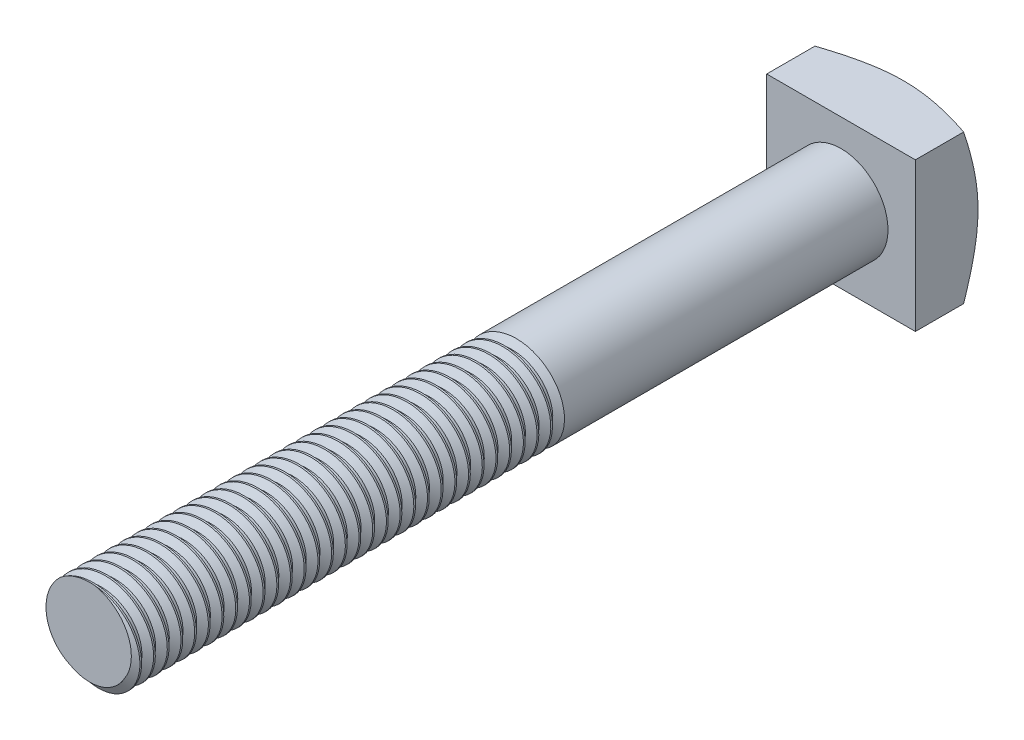
SolidWorks part; units mm, degrees
ref_plane "Front Plane" through (0, 0, 0) normal (0, 0, 1) x (1, 0, 0)
ref_plane "Top Plane" through (0, 0, 0) normal (0, 1, 0) x (1, 0, 0)
ref_plane "Right Plane" through (0, 0, 0) normal (1, 0, 0) x (0, 0, -1)
sketch "Sketch1" plane through (0, 0, 0) normal (0, 0, 1) x (1, 0, 0)
  line L1 (-9.5, -9.5) -> (9.5, -9.5)
  line L2 (-9.5, -9.5) -> (-9.5, 9.5)
  line L3 (-9.5, 9.5) -> (9.5, 9.5)
  line L4 (9.5, -9.5) -> (9.5, 9.5)
  line L5 (-9.5, -9.5) -> (9.5, 9.5) construction
  line L6 (-9.5, 9.5) -> (9.5, -9.5) construction
  point P0 (0, 0)
  dimension "D1" = 19
extrude "Boss-Extrude1" add sketch "Sketch1" along normal blind 8
sketch "Sketch2" plane through (0, 0, 0) normal (0, 1, 0) x (1, 0, 0)
  line L0 (9.5, 0) -> (16.2147, 0)
  line L1 (16.2147, 0) -> (16.2147, -3.1311)
  line L2 (16.2147, -3.1311) -> (9.5, 0)
  line L3 (0, 0) -> (0, 50000) construction
  line L4 (9.5, 0) -> (-9.5, 0) construction
  point P9 (0, 0)
  dimension "D1" = 25
revolve "Cut-Revolve1" cut sketch "Sketch2" angle 360 about L3
sketch "Sketch3" plane through (0, 0, 8) normal (0, 0, 1) x (1, 0, 0)
  circle A0 centre (0, 0) radius 6
extrude "Boss-Extrude2" add sketch "Sketch3" along normal blind 96
thread "Thread1" pitch 1.75 method cut profile "Thread Profile1" start angle 0, offset 2, length 56, pitch 1.75, diameter 12
ref_plane "Plane1" through (-6, 0, 106) normal (0, -1, 0) x (-1, 0, 0)
sketch "Thread Profile1" plane through (-6, 0, 106) normal (0, -1, 0) x (-1, 0, 0)
  line L0 (0, 0) -> (0, 1.75) construction
  line L11 (0, 0) -> (0, 1.5312)
  line L12 (0, 1.5312) -> (-0.9472, 0.9844)
  line L13 (-0.9472, 0.9844) -> (-0.9472, 0.5469)
  line L15 (-0.9472, 0.5469) -> (0, 0)
  line L17 (-0.9472, 0.7656) -> (0, 0.7656) construction
  point P2 (0, 0)
  dimension "Pitch" = 1.75
  dimension "Profile_Angle" = 60
  dimension "Profile_Land" = 0.4375
  dimension "Profile_Height" = 0.9472
